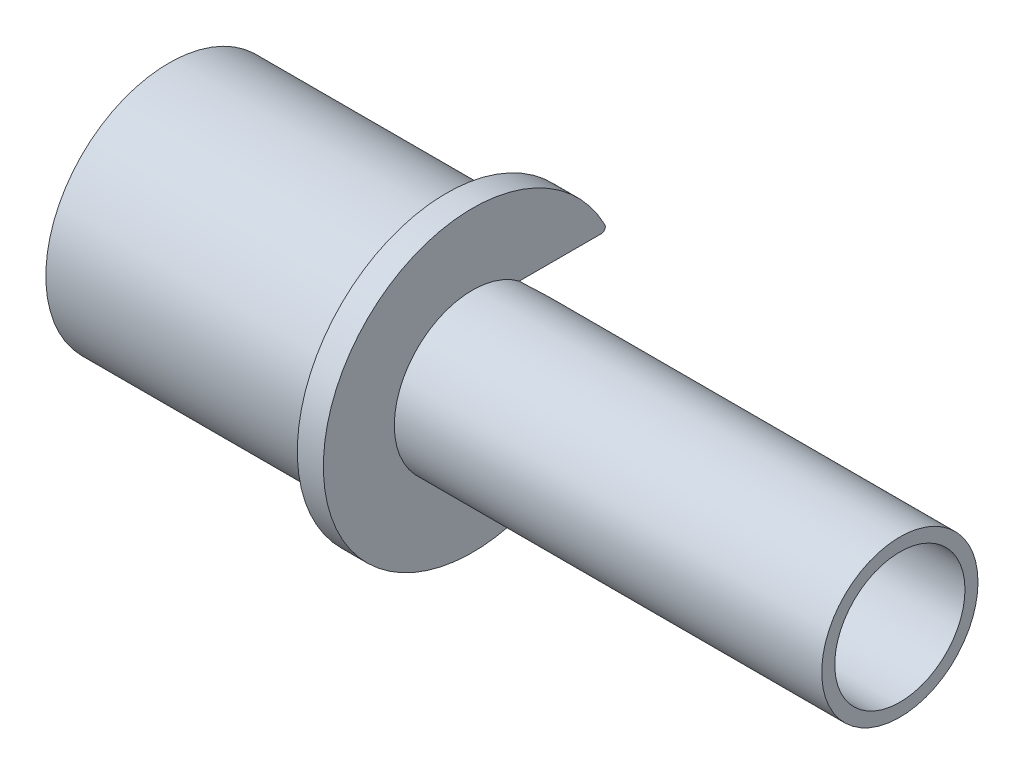
SolidWorks part; units mm, degrees
material "6061-T6 (SS)"
ref_plane "Front Plane" through (0, 0, 0) normal (0, 0, 1) x (1, 0, 0)
ref_plane "Top Plane" through (0, 0, 0) normal (0, 1, 0) x (1, 0, 0)
ref_plane "Right Plane" through (0, 0, 0) normal (1, 0, 0) x (0, 0, -1)
sketch "Sketch1" plane through (0, 0, 0) normal (0, 0, 1) x (1, 0, 0)
  line L0 (0, 0) -> (-16.6687, 0) construction
  line L1 (-4.1125, 3.9687) -> (-4.1125, 4.7625)
  line L2 (-4.1125, 4.7625) -> (-30.1625, 4.7625)
  line L3 (-30.1625, 4.7625) -> (-30.1625, 9.0875)
  line L4 (-30.1625, 9.0875) -> (-31.75, 9.0875)
  line L5 (-31.75, 9.0875) -> (-31.75, 7.5)
  line L6 (-31.75, 7.5) -> (-48.665, 7.5)
  line L7 (-48.665, 7.5) -> (-48.665, 3.9687)
  line L8 (-48.665, 3.9687) -> (-4.1125, 3.9687)
  line L9 (-31.75, -15.27) -> (-31.75, 15.27) construction
  line L10 (-57.15, -5.5562) -> (-57.15, 5.5563) construction
  line L14 (-4.1125, -11.375) -> (-4.1125, 11.375) construction
  dimension "D1" = 7.9375
  dimension "D4" = 15
  dimension "D3" = 9.525
  dimension "D2" = 1.5875
  dimension "D5" = 1.5875
  dimension "D6" = 8.485
revolve "Revolve1" add sketch "Sketch1" angle 360 about L0
sketch "Sketch2" plane through (-4.1125, 0, 0) normal (1, 0, 0) x (0, 0, -1)
  line L0 (1.3441, 3.7342) -> (8.2848, 3.7342)
  line L1 (8.2848, -3.7342) -> (1.3441, -3.7342)
  line L2 (0, 0) -> (14.3216, 0) construction
  circle A0 centre (0, 0) radius 3.9687 construction
  circle A1 centre (0, 0) radius 9.0875 construction
  arc A2 (1.3441, 3.7342) -> (1.3441, -3.7342) centre (0, 0) cw
  arc A3 (8.2848, 3.7342) -> (8.2848, -3.7342) centre (0, 0) cw
  arc A4 (3.6742, 3.7342) -> (3.6742, -3.7342) centre (0, 0) cw construction
  circle A5 centre (5.2387, 0) radius 1.27 construction
  circle A6 centre (4.623, 2.4642) radius 1.27 construction
  circle A7 centre (4.623, -2.4642) radius 1.27 construction
  dimension "D1" = 1.27
  dimension "D2" = 2.54
extrude "Cut-Extrude1" [suppressed] cut sketch "Sketch2" against normal through all both
sketch "Sketch3" plane through (0, 0, 0) normal (0, 0, 1) x (1, 0, 0)
  line L0 (-48.665, 3.81) -> (-48.665, -3.81)
  line L1 (-48.665, 7.5) -> (-48.665, -7.5) construction
  line L2 (-48.665, -3.81) -> (-30.1625, -3.81)
  line L4 (-30.1625, 3.81) -> (-48.665, 3.81)
  line L5 (-26.9875, -0.635) -> (-26.9875, 0.635)
  line L6 (-26.9875, 0) -> (0, 0) construction
  line L8 (-30.1625, -9.0875) -> (-30.1625, 9.0875) construction
  arc A1 (-30.1625, -3.81) -> (-26.9875, -0.635) centre (-30.1625, -0.635) ccw
  arc A2 (-26.9875, 0.635) -> (-30.1625, 3.81) centre (-30.1625, 0.635) ccw
  dimension "D1" = 7.62
  dimension "D2" = 3.175
extrude "Cut-Extrude2" cut sketch "Sketch3" against normal up to next
fillet "Fillet1" radius 0.254 4 edges at (-30.9562, 3.81, -8.2502) (-30.9562, -3.81, -8.2502) (-40.2075, -3.81, -6.4602) (-40.2075, 3.81, -6.4602)
equation "\"bearing1\"=0.273438"
equation "\"D1@Sketch1\"=5/16"
equation "\"D4@Sketch1\"=15mm"
equation "\"D6@Sketch1\"=.275+1.5mm"
